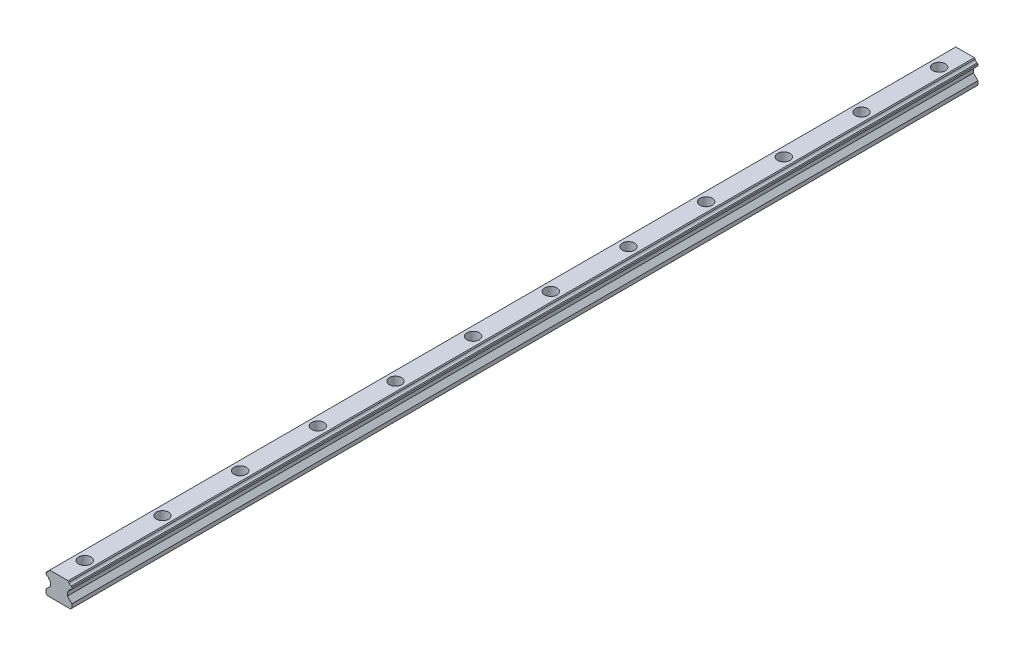
SolidWorks part; units mm, degrees
material "Plain Carbon Steel"
ref_plane "Front Plane" through (0, 0, 0) normal (0, 0, 1) x (1, 0, 0)
ref_plane "Top Plane" through (0, 0, 0) normal (0, 1, 0) x (1, 0, 0)
ref_plane "Right Plane" through (0, 0, 0) normal (1, 0, 0) x (0, 0, -1)
sketch "Sketch1" plane through (0, 0, 0) normal (0, 0, 1) x (1, 0, 0)
  line L0 (0, 13.3681) -> (0, -3.2505) construction
  line L1 (-6.55, 1.465) -> (-6.55, -1.465)
  line L2 (-6.55, 0) -> (0, 0) construction
  line L3 (-6.55, -1.465) -> (-10, -4.915)
  line L4 (-10, -4.915) -> (-10, -7.915)
  line L5 (-10, -7.915) -> (-9, -8.915)
  line L6 (-9, -8.915) -> (0, -8.915)
  line L7 (-6.55, 1.465) -> (-7.7681, 2.6831)
  line L8 (-10, 4.915) -> (-10, 6.245)
  line L9 (-10, 6.245) -> (-9.4697, 6.7753)
  line L10 (-7.16, 9.085) -> (0, 9.085)
  line L11 (-10, 4.915) -> (-10, -4.915) construction
  line L12 (-10, 5.58) -> (0, 5.58) construction
  line L13 (-7.7681, 8.4769) -> (-7.16, 9.085)
  line L14 (-9.4697, 4.3847) -> (-10, 4.915)
  line L15 (0, 9.085) -> (0, -8.915)
  arc A0 (-9.4697, 6.7753) -> (-7.7681, 8.4769) centre (-9.7486, 8.7558) ccw
  arc A1 (-9.4697, 4.3847) -> (-7.7681, 2.6831) centre (-9.7486, 2.4042) cw
  dimension "D10" = 4
  dimension "D1" = 2.93
  dimension "D2" = 6.55
  dimension "D3" = 9
  dimension "D4" = 7.16
  dimension "D5" = 3
  dimension "D6" = 1.33
  dimension "D7" = 18
  dimension "D8" = 45
  dimension "D9" = 45
  dimension "D11" = 0.75
  dimension "D12" = 0.86
extrude "Boss-Extrude1" add sketch "Sketch1" along normal blind 350
mirror "Mirror1" about plane through (0, 9.085, 350) normal (-1, 0, 0) of "Boss-Extrude1"
sketch "Sketch2" plane through (0, 9.085, 0) normal (0, 1, 0) x (1, 0, 0)
  line L0 (0, 130.187) -> (0, 31.9327) construction
  line L1 (7.16, 0) -> (-7.16, 0) construction
  circle A0 centre (0, -30) radius 3
  dimension "D1" = 6
  dimension "D2" = 30
extrude "Cut-Extrude1" cut sketch "Sketch2" against normal through all
sketch "Sketch3" plane through (0, 9.085, 0) normal (0, 1, 0) x (1, 0, 0)
  circle A0 centre (0, -30) radius 4.75
  dimension "D1" = 9.5
extrude "Cut-Extrude2" cut sketch "Sketch3" against normal blind 8.5
pattern_linear "LPattern1" count 100 spacing 60 along (0, 0, 1) of "Cut-Extrude1", "Cut-Extrude2"
mirror "Mirror2" about plane through (-9.7486, 2.4042, 0) normal (0, 0, -1) of bodies 106
equation "\"length\"= 700mm"
equation "\"D1@Boss-Extrude1\"=\"length\" /2"
